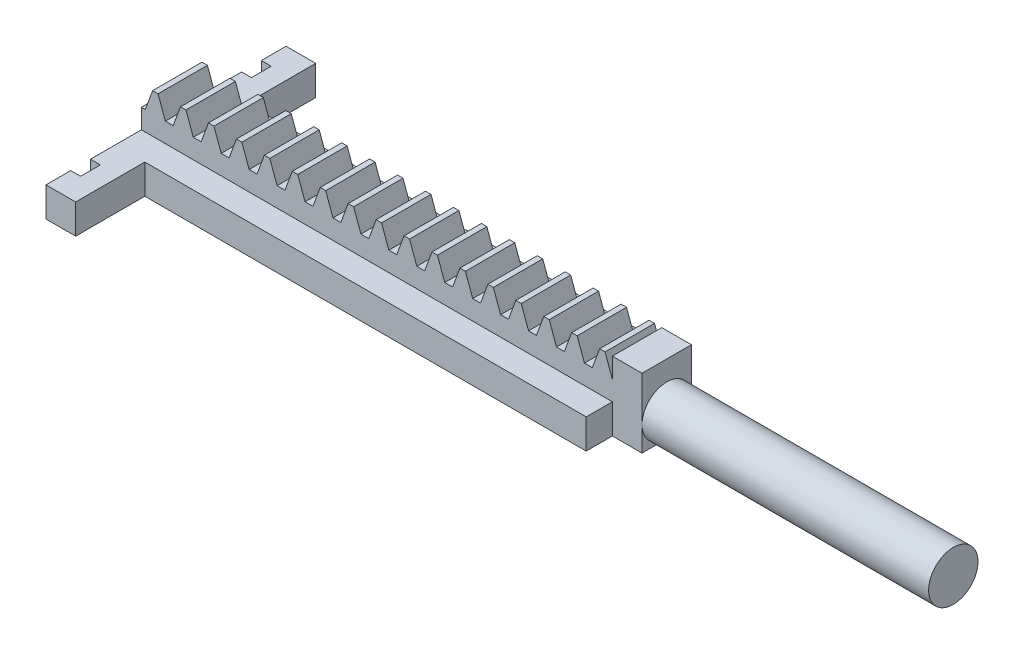
SolidWorks part; units mm, degrees
extrude "Blank" add sketch "BlankSke" against normal blind 5
sketch "BlankSke" plane through (0, 0, 0) normal (0, 0, 1) x (1, 0, 0)
  line L1 (0, 0) -> (47.667, 0)
  line L2 (0, 0) -> (0, 7)
  line L3 (0, 7) -> (47.667, 7)
  line L4 (47.667, 0) -> (47.667, 7)
  dimension "Length" = 47.667
  dimension "Blank_height" = 7
ref_plane "Plane1" through (0, 0, 0) normal (0, 0, 1) x (1, 0, 0)
ref_plane "Plane2" through (0, 0, 0) normal (0, 1, 0) x (1, 0, 0)
ref_plane "Plane3" through (0, 0, 0) normal (1, 0, 0) x (0, 0, -1)
other "Configuration Table"
sketch "HoldingSke" plane through (0, 0, 0) normal (0, 1, 0) x (1, 0, 0)
  line L0 (0, 0) -> (0.1546, 1.1003)
  line L1 (-15, 0) -> (100, 0) construction
  line L2 (0, 0) -> (-2.1039, 2.3779)
  line L3 (0, 0) -> (-11.863, 4.5341)
  line L4 (0, 0) -> (7.9495, 3.3743)
  line L5 (0, 0) -> (-23.7986, -8.8762)
  line L6 (0, 0) -> (-10.5278, -7.1032)
  line L9 (-71.009, 38.7566) -> (-14.6274, 59.2778)
  line L10 (-76.2, 3.2779) -> (-66.2, 3.2779)
  line L11 (0, 0) -> (-10, 0)
  line L12 (-76.2, 101.6) -> (-76.166, 101.6)
  line L13 (24.9733, 27.94) -> (52.9518, 28.4284)
  line L14 (24.9733, 27.94) -> (24.9743, 27.94)
  line L15 (24.9733, 27.94) -> (100.4006, 29.5858)
  circle A0 centre (0, 0) radius 19.05
  circle A1 centre (0, 0) radius 5
  circle A2 centre (0, 0) radius 12.7
  dimension "Num_teeth" = 23
  dimension "Width" = 10
sketch "TooCutSkeIll" plane through (0, 0, 0) normal (0, 0, 1) x (1, 0, 0)
  line L0 (0.2917, 6.9763) -> (-0.4535, 9.0237)
  line L1 (-0.2411, 8.875) -> (0.2411, 8.875)
  line L2 (0.4535, 9.0237) -> (-0.2917, 6.9763)
  line L3 (47.667, 7) -> (0, 7) construction
  line L4 (0, 0) -> (0, 64.897) construction
  line L5 (-13.208, 10) -> (12.954, 10) construction
  line L6 (0, 0) -> (47.667, 0) construction
  line L7 (0.8089, 10) -> (0.8089, 48.7463) construction
  line L8 (-0.8089, 10) -> (-0.8089, 48.7463) construction
  line L9 (-0.2578, 7) -> (-0.2578, 10.9254)
  line L10 (0.2578, 7) -> (0.2578, 10.9254)
  line L11 (0.2578, 10.9254) -> (-0.2578, 10.9254)
  arc A0 (0.2411, 8.875) -> (0.4535, 9.0237) centre (0.2411, 9.101) ccw
  arc A1 (-0.4535, 9.0237) -> (-0.2411, 8.875) centre (-0.2411, 9.101) ccw
  arc A2 (-0.2578, 7) -> (-0.2917, 6.9763) centre (-0.2578, 6.964) ccw
  arc A3 (0.2917, 6.9763) -> (0.2578, 7) centre (0.2578, 6.964) ccw
  dimension "Addendum_plus" = 0.9254
  dimension "Pressure_angle" = 20
  dimension "Gap_width" = 1.6177
  dimension "Dedendum" = 1.125
extrude "ToothCutIll" [suppressed] cut sketch "TooCutSkeIll" against normal through all
sketch "TooCutSkeSim" plane through (0, 0, 0) normal (0, 0, 1) x (1, 0, 0)
  line L0 (0.3994, 4.975) -> (-0.3994, 4.975)
  line L1 (1.1457, 7.0254) -> (0.3994, 4.975)
  line L2 (0, 17.4625) -> (0, 53.467) construction
  line L3 (1.1457, 7.0254) -> (-1.1457, 7.0254)
  line L6 (-1.1457, 7.0254) -> (-0.3994, 4.975)
  line L9 (-0.8089, 6.1) -> (0.8089, 6.1) construction
  line L10 (0, 0) -> (47.667, 0) construction
  line L11 (0.8089, 6.1) -> (0.8089, 53.467) construction
  line L12 (-0.8089, 6.1) -> (-0.8089, 53.467) construction
  dimension "Addendum_plus" = 0.9254
  dimension "Pitch_height" = 6.1
  dimension "Pressure_angle" = 20
  dimension "Gap_width" = 1.6177
  dimension "Dedendum" = 1.125
extrude "ToothCutSim" cut sketch "TooCutSkeSim" against normal through all
pattern_linear "TeethCuts" count 18 spacing 2.8274 along (1, 0, 0) of "ToothCutSim"
sketch "Sketch1" plane through (47.667, 0, 0) normal (1, 0, 0) x (0, 0, -1)
  line L0 (2.5, 4.975) -> (2.5, 0) construction
  line L1 (0, 4.975) -> (5, 4.975) construction
  line L2 (5, 0) -> (0, 0) construction
  line L3 (0, 2.4875) -> (5, 2.4875) construction
  line L4 (0, 0) -> (0, 4.975) construction
  line L5 (5, 0) -> (5, 4.975) construction
  circle A0 centre (2.5, 2.4875) radius 2.5
  dimension "D1" = 5
extrude "Boss-Extrude1" add sketch "Sketch1" along normal blind 32
sketch "Sketch2" plane through (0, 0, 0) normal (-1, 0, 0) x (0, 0, 1)
  line L0 (-2.5, 4.975) -> (-2.5, 0) construction
  line L1 (-7.6475, 3) -> (-5, 3)
  line L2 (-7.6475, 3) -> (-7.6475, 0)
  line L3 (-7.6475, 0) -> (-5, 0)
  line L4 (-5, 3) -> (-5, 0)
  line L5 (-7.6475, 3) -> (-5, 0) construction
  line L6 (-7.6475, 0) -> (-5, 3) construction
  line L7 (-5, 4.975) -> (0, 4.975) construction
  line L8 (-5, 0) -> (0, 0) construction
  line L9 (2.6475, 0) -> (0, 0)
  line L10 (0, 3) -> (0, 0)
  line L11 (2.6475, 3) -> (0, 3)
  line L12 (2.6475, 3) -> (2.6475, 0)
  point P0 (-6.3237, 1.5)
  dimension "D1" = 3
extrude "Boss-Extrude2" add sketch "Sketch2" against normal up to surface (47.667 mm away) up to face at (47.667, 0.6847, -4.4096)
sketch "Sketch3" plane through (47.667, 0, 0) normal (1, 0, 0) x (0, 0, -1)
  line L1 (0, 0) -> (5, 0)
  line L2 (0, 0) -> (0, 7)
  line L3 (0, 7) -> (5, 7)
  line L4 (5, 0) -> (5, 7)
  line L5 (0, 3) -> (0, 4.975) construction
  line L6 (5, 3) -> (5, 4.975) construction
  dimension "D1" = 7
extrude "Boss-Extrude3" add sketch "Sketch3" along normal blind 3
sketch "Sketch4" plane through (0, 0, -7.6475) normal (0, 0, -1) x (-1, 0, 0)
  line L0 (-47.667, 0) -> (0, 0) construction
  line L1 (-3, 3) -> (0, 3)
  line L2 (-3, 3) -> (-3, 0)
  line L3 (-3, 0) -> (0, 0)
  line L4 (0, 3) -> (0, 0)
  line L5 (-3, 3) -> (0, 0) construction
  line L6 (-3, 0) -> (0, 3) construction
  line L7 (-47.667, 3) -> (0, 3) construction
  line L8 (0, 3) -> (0, 0) construction
  point P0 (-1.5, 1.5)
  dimension "D1" = 3
extrude "Boss-Extrude4" add sketch "Sketch4" along normal blind 7
ref_plane "Plane4" through (0, 0, -2.5) normal (0, 0, -1) x (-1, 0, 0)
mirror "Mirror1" about plane through (0, 0, -2.5) normal (0, 0, -1) of "Boss-Extrude4"
sketch "Sketch5" plane through (0, 0, 0) normal (-1, 0, 0) x (0, 0, 1)
  line L0 (-14.6475, 0) -> (9.6475, 0) construction
  line L1 (-12.1475, 3) -> (-10.1475, 3)
  line L2 (-12.1475, 3) -> (-12.1475, 0)
  line L3 (-12.1475, 0) -> (-10.1475, 0)
  line L4 (-10.1475, 3) -> (-10.1475, 0)
  line L5 (-12.1475, 3) -> (-10.1475, 0) construction
  line L6 (-12.1475, 0) -> (-10.1475, 3) construction
  line L7 (-5, 3) -> (-14.6475, 3) construction
  line L8 (-14.6475, 0) -> (-14.6475, 3) construction
  point P0 (-11.1475, 1.5)
  dimension "D1" = 2.5
  dimension "D2" = 2
extrude "Cut-Extrude1" cut sketch "Sketch5" against normal blind 1
ref_plane "Plane5" through (0, 0, -2.5) normal (0, 0, -1) x (-1, 0, 0)
mirror "Mirror2" about plane through (0, 0, -2.5) normal (0, 0, -1) of "Cut-Extrude1"
equation "' \"Module@HoldingSke\" = 6.35"
equation "' \"Num_teeth@HoldingSke\" = 12"
equation "' \"Ap@HoldingSke\" =  20"
equation "' \"Ap@HoldingSke\" = 20"
equation "' \"Width@HoldingSke\" = 0.25 * 25.4"
equation "' \"Show_teeth@HoldingSke\" = 500"
equation "' \"Backlash@HoldingSke\" = 0.009 * 25.4"
equation "' \"Addendum_fac@HoldingSke\" = 1.0"
equation "' \"Dedendum_fac@HoldingSke\" = 1.25"
equation "' \"Dedendum_add@HoldingSke\" = 0.00005 * 25.4"
equation "' \"Clearance_fac@HoldingSke\" = 0.25"
equation "' \"Pitch_height@HoldingSke\" = 1 * 25.4"
equation "' \"Length@HoldingSke\" = 4.71 * 25.4"
equation "\"Pitch@HoldingSke\" = 1 / \"Module@HoldingSke\""
equation "\"MPH@HoldingSke\" = \"Dedendum_fac@HoldingSke\" / \"Pitch@HoldingSke\" + 2 * \"Dedendum_add@HoldingSke\" + 0.002 * 25.4"
equation "\"MPH@HoldingSke\" = ((sgn( \"MPH@HoldingSke\" - \"Pitch_height@HoldingSke\")+1)*( \"MPH@HoldingSke\" - \"Pitch_height@HoldingSke\"))/2 + \"Pitch_height@HoldingSke\""
equation "\"Pressure_angle@TooCutSkeIll\" = \"Ap@HoldingSke\""
equation "\"Addendum_plus@TooCutSkeIll\" =  \"Addendum_fac@HoldingSke\"  / \"Pitch@HoldingSke\" + 0.001 *25.4"
equation "\"Dedendum@TooCutSkeIll\" = \"Dedendum_fac@HoldingSke\"  / \"Pitch@HoldingSke\""
equation "\"Pitch_height@TooCutSkeIll\" =  \"MPH@HoldingSke\""
equation "\"Gap_width@TooCutSkeIll\" = 3.14159265 / 2 / \"Pitch@HoldingSke\" + 6 * \"Backlash@HoldingSke\""
equation "\"Pressure_angle@TooCutSkeSim\" = \"Ap@HoldingSke\""
equation "\"Addendum_plus@TooCutSkeSim\" =  \"Addendum_fac@HoldingSke\"  / \"Pitch@HoldingSke\" + 0.001 * 25.4"
equation "\"Dedendum@TooCutSkeSim\" = \"Dedendum_fac@HoldingSke\"  / \"Pitch@HoldingSke\""
equation "\"Gap_width@TooCutSkeSim\" = 3.14159265 / 2 / \"Pitch@HoldingSke\" + 6 * \"Backlash@HoldingSke\""
equation "\"Root_fillet@TooCutSkeIll\" = \"Clearance_fac@HoldingSke\" / \"Pitch@HoldingSke\" + \"Dedendum_add@HoldingSke\""
equation "\"Break_rad@TooCutSkeIll\" = 0.02 / \"Pitch@HoldingSke\" * 2"
equation "\"Linear_pitch@TeethCuts\" = 3.14159265 / \"Pitch@HoldingSke\""
equation "\"Num_teeth@HoldingSke\" = int( ( \"Length@HoldingSke\" + 0 ) / (3.14159265 / \"Pitch@HoldingSke\")) + 0.9999  + 1"
equation " \"Num_teeth@TeethCuts\" = ((sgn( \"Num_teeth@TeethCuts\" - \"Num_teeth@HoldingSke\" )-1)*( \"Num_teeth@TeethCuts\" - \"Num_teeth@HoldingSke\" ))/-2+ \"Num_teeth@HoldingSke\""
equation " \"Num_teeth@TeethCuts\" = ((sgn( \"Num_teeth@TeethCuts\" - 2.0)+1)*( \"Num_teeth@TeethCuts\" - 2.0))/2 +2.0"
